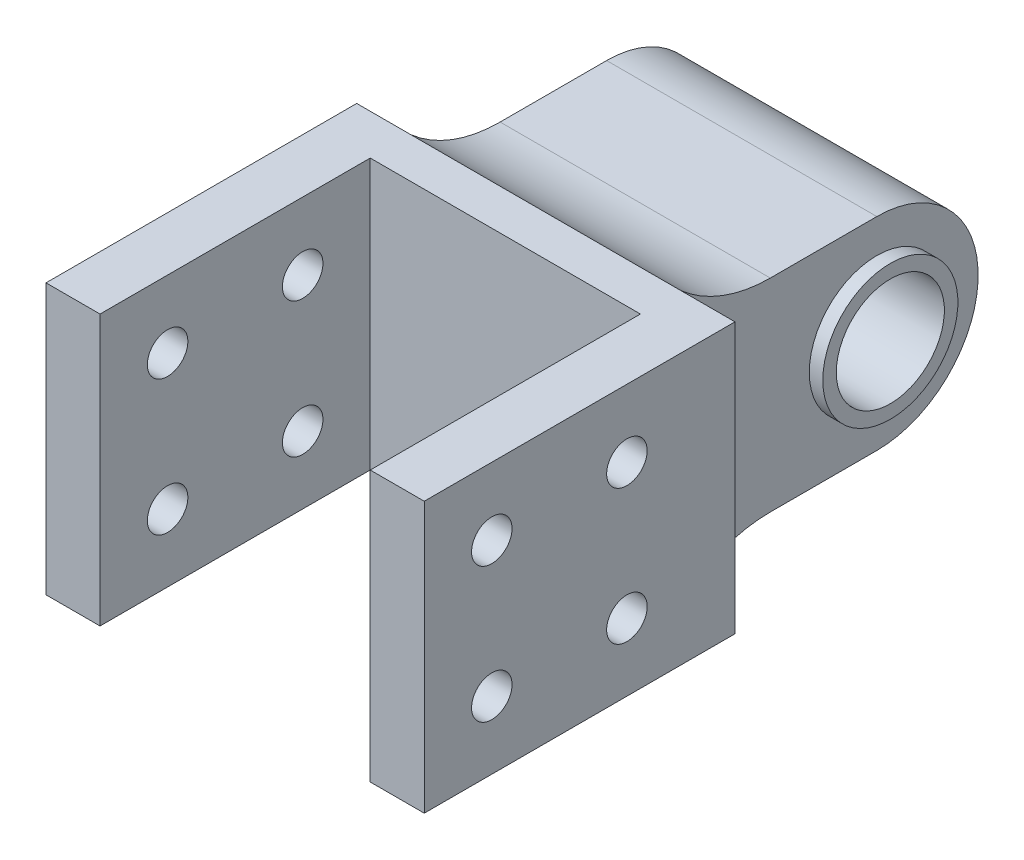
SolidWorks part; units mm, degrees
material "1060 合金"
ref_plane "前视基准面" through (0, 0, 0) normal (0, 0, 1) x (1, 0, 0)
ref_plane "上视基准面" through (0, 0, 0) normal (0, 1, 0) x (1, 0, 0)
ref_plane "右视基准面" through (0, 0, 0) normal (1, 0, 0) x (0, 0, -1)
sketch "草图1" plane through (0, 0, 0) normal (0, 0, 1) x (1, 0, 0)
  line L1 (-14, -10) -> (14, -10)
  line L2 (-14, -10) -> (-14, 10)
  line L3 (-14, 10) -> (14, 10)
  line L4 (14, -10) -> (14, 10)
  line L5 (-14, -10) -> (14, 10) construction
  line L6 (-14, 10) -> (14, -10) construction
  point P0 (0, 0)
  dimension "D1" = 20
  dimension "D2" = 28
extrude "凸台-拉伸1" add sketch "草图1" along normal blind 20
sketch "草图3" plane through (0, 0, 0) normal (0, 0, -1) x (-1, 0, 0)
  line L1 (-14, -10) -> (14, -10)
  line L2 (-14, -10) -> (-14, 10)
  line L3 (-14, 10) -> (14, 10)
  line L4 (14, -10) -> (14, 10)
  line L5 (-14, -10) -> (14, 10) construction
  line L6 (-14, 10) -> (14, -10) construction
  point P0 (0, 0)
  dimension "D1" = 20
  dimension "D2" = 28
extrude "凸台-拉伸2" add sketch "草图3" along normal blind 3 from surface starting at plane "前视基准面"
sketch "草图4" plane through (0, 0, 0) normal (1, 0, 0) x (0, 0, -1)
  line L0 (17.5, 7.5) -> (3, 7.5)
  line L1 (3, 10) -> (3, -10) construction
  line L2 (3, 7.5) -> (3, -7.5)
  line L3 (3, -7.5) -> (17.5, -7.5)
  line L4 (-20, 10) -> (3, 10) construction
  arc A0 (17.5, -7.5) -> (17.5, 7.5) centre (17.5, 0) ccw
  circle A1 centre (17.5, 0) radius 4
  dimension "D1" = 15
  dimension "D2" = 8
  dimension "D3" = 14.5
  dimension "D4" = 10
extrude "凸台-拉伸3" add sketch "草图4" along normal mid plane 20
sketch "草图5" plane through (-10, 0, 0) normal (-1, 0, 0) x (0, 0, 1)
  circle A0 centre (-17.5, 0) radius 4
  circle A1 centre (-17.5, 0) radius 5
  dimension "D1" = 8
  dimension "D2" = 10
extrude "凸台-拉伸4" add sketch "草图5" along normal blind 1
mirror "镜向1" about plane through (0, 0, 0) normal (1, 0, 0) of "凸台-拉伸4"
fillet "圆角1" radius 10 2 edges at (0, -7.5, -3) (0, 7.5, -3)
sketch "草图11" plane through (0, -10, 0) normal (0, -1, 0) x (1, 0, 0)
  line L0 (-14, 20) -> (14, 20) construction
  line L1 (-10, 20) -> (10, 20)
  line L2 (-10, 20) -> (-10, 0)
  line L3 (-10, 0) -> (10, 0)
  line L4 (10, 20) -> (10, 0)
  line L5 (14, 20) -> (14, -3) construction
  dimension "D1" = 20
  dimension "D2" = 4
extrude "切除-拉伸1" cut sketch "草图11" against normal blind 20
sketch "草图12" plane through (14, 0, 0) normal (1, 0, 0) x (0, 0, -1)
  line L0 (-20, 10) -> (3, 10) construction
  line L1 (-15, -5) -> (-5, -5) construction
  line L2 (-15, -5) -> (-15, 5) construction
  line L3 (-15, 5) -> (-5, 5) construction
  line L4 (-5, -5) -> (-5, 5) construction
  line L5 (-15, -5) -> (-5, 5) construction
  line L6 (-15, 5) -> (-5, -5) construction
  line L7 (-20, -10) -> (-20, 10) construction
  circle A0 centre (-15, 5) radius 1.5
  circle A1 centre (-5, 5) radius 1.5
  circle A2 centre (-5, -5) radius 1.5
  circle A3 centre (-15, -5) radius 1.5
  point P0 (-10, 0)
  dimension "D4" = 3
  dimension "D5" = 3
  dimension "D6" = 3
  dimension "D7" = 3
  dimension "D1" = 10
  dimension "D2" = 10
  dimension "D3" = 10
extrude "切除-拉伸2" cut sketch "草图12" against normal blind 40
sketch "草图14" plane through (0, 0, 0) normal (1, 0, 0) x (0, 0, -1)
  line L0 (17.5, 8.2123) -> (17.5, -9.4671) construction
  line L1 (12.4, -1.5) -> (14.6, -1.5)
  line L2 (12.4, -1.5) -> (12.4, 1.5)
  line L3 (12.4, 1.5) -> (14.6, 1.5)
  line L4 (14.6, -1.5) -> (14.6, 1.5)
  line L5 (12.4, -1.5) -> (14.6, 1.5) construction
  line L6 (12.4, 1.5) -> (14.6, -1.5) construction
  point P0 (13.5, 0)
  dimension "D1" = 3
  dimension "D2" = 2.2
  dimension "D3" = 2.9
extrude "切除-拉伸3" [suppressed] cut sketch "草图14" against normal mid plane 40
